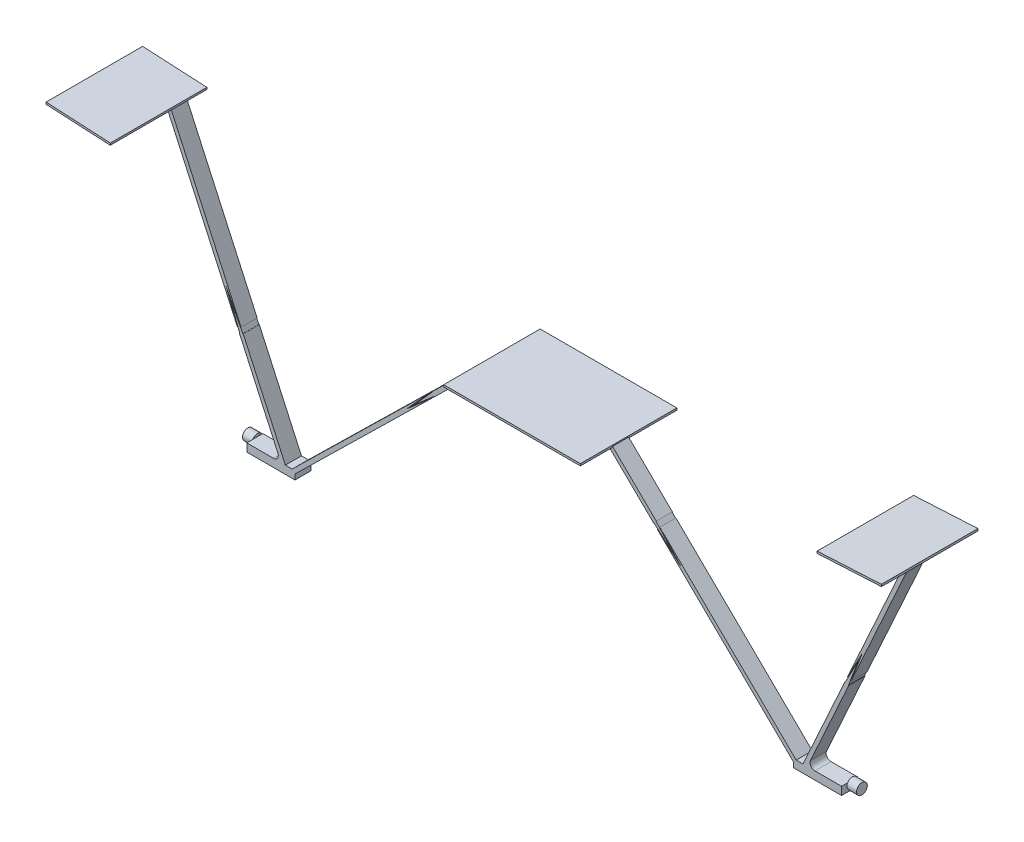
SolidWorks part; units mm, degrees
note: The reader was unsure of these and kept them because the rebuilt part matched: shared geometry of "Sketch1<4>", "Sketch1<6>", "Sketch1<7>", "Sketch1<8>".
ref_plane "Front Plane" through (0, 0, 0) normal (0, 0, 1) x (1, 0, 0)
ref_plane "Top Plane" through (0, 0, 0) normal (0, 1, 0) x (1, 0, 0)
ref_plane "Right Plane" through (0, 0, 0) normal (1, 0, 0) x (0, 0, -1)
sketch "Sketch1" plane through (0, 0, 0) normal (0, 0, 1) x (1, 0, 0)
  line L0 (0, 28.575) -> (748.2731, 67.7903) construction
  line L1 (-50.8, 28.575) -> (50.8, 28.575) construction
  line L2 (-50.8, 28.575) -> (-50.8, -28.575) construction
  line L3 (-50.8, -28.575) -> (50.8, -28.575) construction
  line L4 (50.8, 28.575) -> (50.8, -28.575) construction
  line L5 (-50.8, 28.575) -> (50.8, -28.575) construction
  line L6 (-50.8, -28.575) -> (50.8, 28.575) construction
  line L7 (0, 0) -> (0, -177.8) construction
  line L8 (0, -177.8) -> (203.2, -177.8) construction
  line L9 (0, 28.575) -> (304.3823, 44.527) construction
  line L10 (50.8, -28.575) -> (203.2, -177.8) construction
  line L11 (304.3823, 44.527) -> (203.2, -177.8) construction
  line L12 (0, -28.575) -> (50.8, -28.575)
  line L16 (0, -28.575) -> (0, -30.1625)
  line L18 (279.0171, 43.1977) -> (329.7475, 45.8563)
  line L19 (279.0171, 43.1977) -> (329.7475, 45.8563)
  line L20 (279.0171, 43.1977) -> (279.1002, 41.6123)
  line L21 (329.7475, 45.8563) -> (329.8306, 44.271)
  line L22 (279.1002, 41.6123) -> (329.8306, 44.271)
  line L23 (196.7149, -177.8) -> (234.8149, -177.8)
  line L24 (196.7149, -177.8) -> (196.7149, -171.45)
  line L25 (234.8149, -177.8) -> (234.8149, -171.45)
  line L26 (196.7149, -171.45) -> (234.8149, -171.45)
  line L27 (203.2, -177.8) -> (203.2, -146.05) construction
  line L28 (53.975, -29.4621) -> (198.984, -171.45)
  line L29 (50.1522, -30.1625) -> (196.7149, -173.6718)
  line L30 (207.8341, -171.45) -> (305.4279, 42.9921)
  line L31 (301.8543, 42.8048) -> (204.3457, -171.45)
  line L32 (0, -30.1625) -> (53.975, -30.1625)
  line L33 (53.975, -30.1625) -> (53.975, -28.575)
  line L34 (53.975, -28.575) -> (50.8, -28.575)
  point P0 (0, 0)
  point P14 (54.7565, -30.1625)
  point P16 (0, 0)
  point P19 (304.3823, 44.527)
  point P36 (0, 0)
  dimension "D1" = 101.6
  dimension "D2" = 57.15
  dimension "D3" = 749.3
  dimension "D4" = 3
  dimension "D5" = 177.8
  dimension "D6" = 203.2
  dimension "D7" = 304.8
  dimension "D8" = 3.175
  dimension "D9" = 1.5875
  dimension "D10" = 50.8
  dimension "D11" = 1.5875
  dimension "D12" = 6.35
  dimension "D13" = 31.75
  dimension "D14" = 38.1
  dimension "D15" = 1.5875
  dimension "D16" = 1.5875
  dimension "D17" = 1.5875
  dimension "D18" = 1.5875
extrude "Boss-Extrude1" add sketch "Sketch1" along normal mid plane 76.2 contours L12 L34 L33 L32 L16
extrude "Boss-Extrude2" add sketch "Sketch1<4>" along normal blind 76.2 separate body contours L20 L22 L21 L18
sketch "Sketch1<4>" plane through (0, 0, 0) normal (0, 0, 1) x (1, 0, 0) same geometry as "Sketch1"
extrude "Boss-Extrude8" add sketch "Sketch1<6>" along normal blind 12.7 separate body contours L26 L24 L23 L25
sketch "Sketch1<6>" plane through (0, 0, 0) normal (0, 0, 1) x (1, 0, 0) same geometry as "Sketch1"
extrude "Boss-Extrude9" add sketch "Sketch1<7>" along normal blind 12.7
sketch "Sketch1<7>" plane through (0, 0, 0) normal (0, 0, 1) x (1, 0, 0) same geometry as "Sketch1"
extrude "Boss-Extrude10" add sketch "Sketch1<8>" along normal blind 12.7 contours L22 L31 L26 L30
sketch "Sketch1<8>" plane through (0, 0, 0) normal (0, 0, 1) x (1, 0, 0) same geometry as "Sketch1"
sketch "Sketch2" plane through (234.8149, 0, 0) normal (1, 0, 0) x (0, 0, -1)
  line L0 (0, -177.8) -> (0, -171.45) construction
  line L1 (-12.7, -177.8) -> (0, -177.8) construction
  circle A0 centre (-4.2625, -173.5375) radius 4.2625
  dimension "D1" = 8.525
extrude "Boss-Extrude11" add sketch "Sketch2" along normal blind 7.62
sketch "printBeds" plane through (0, 0, 0) normal (0, 0, 1) x (1, 0, 0)
  line L0 (125.7236, -68.1503) -> (0, 57.5733) construction
  line L1 (125.7236, -68.1503) -> (0, -193.8739) construction
  line L2 (0, 57.5733) -> (-125.7236, -68.1503) construction
  line L3 (0, -193.8739) -> (-125.7236, -68.1503) construction
  line L4 (291.5515, 61.4763) -> (213.4818, -98.2672) construction
  line L5 (291.5515, 61.4763) -> (451.2949, -16.5934) construction
  line L6 (213.4818, -98.2672) -> (373.2252, -176.3369) construction
  line L7 (451.2949, -16.5934) -> (373.2252, -176.3369) construction
  line L8 (258.004, -217.3263) -> (253.5037, -39.5833) construction
  line L9 (258.004, -217.3263) -> (80.261, -221.8266) construction
  line L10 (253.5037, -39.5833) -> (75.7607, -44.0836) construction
  line L11 (80.261, -221.8266) -> (75.7607, -44.0836) construction
  dimension "D1" = 177.8
  dimension "D2" = 177.8
  dimension "D3" = 177.8
  dimension "D4" = 177.8
  dimension "D5" = 177.8
  dimension "D6" = 177.8
fillet "Fillet1" radius 3.81 4 edges at (207.8341, -171.45, 6.35) (305.4279, 42.9921, 6.35) (301.8543, 42.8048, 6.35) (50.1522, -30.1625, 6.35)
sketch "Sketch3" plane through (0, 0, 38.1) normal (0, 0, 1) x (1, 0, 0)
  line L0 (86.2682, -65.5261) -> (88.4895, -63.2575) construction
  line L7 (51.2631, -31.2502) -> (196.7149, -173.6718) construction
  line L14 (53.975, -29.4621) -> (198.984, -171.45) construction
  line L15 (86.2682, -65.5261) -> (105.5274, -82.1623) construction
  line L16 (105.5274, -82.1623) -> (88.4895, -63.2575) construction
  line L17 (105.5274, -82.1623) -> (87.3788, -64.3918) construction
  line L32 (86.1048, -65.7153) -> (108.391, -84.9662)
  line L33 (108.391, -84.9662) -> (88.6752, -63.0901)
  line L52 (86.4316, -65.3369) -> (102.6638, -79.3583)
  line L53 (102.6638, -79.3583) -> (88.3038, -63.4249)
  line L54 (86.1048, -65.7153) -> (86.4316, -65.3369)
  line L55 (88.6752, -63.0901) -> (88.3038, -63.4249)
  line L56 (237.6392, -98.2945) -> (240.529, -99.6097) construction
  line L57 (299.2551, 37.0934) -> (204.3457, -171.45) construction
  line L58 (210.2863, -166.0618) -> (304.4697, 40.8866) construction
  line L59 (237.6392, -98.2945) -> (249.6055, -75.8336) construction
  line L60 (249.6055, -75.8336) -> (240.529, -99.6097) construction
  line L61 (249.6055, -75.8336) -> (239.0841, -98.9521) construction
  line L62 (237.8599, -98.412) -> (247.9453, -79.4814)
  line L63 (247.9453, -79.4814) -> (240.2955, -99.5205)
  line L64 (237.4186, -98.1769) -> (251.2656, -72.1858)
  line L65 (251.2656, -72.1858) -> (240.7626, -99.6988)
  line L66 (240.2955, -99.5205) -> (240.7626, -99.6988)
  line L67 (237.4186, -98.1769) -> (237.8599, -98.412)
  dimension "D1" = 1.5875
  dimension "D2" = 0.25
  dimension "D3" = 0.25
  dimension "D4" = 25.4
  dimension "D5" = 1.5875
  dimension "D6" = 25.4
  dimension "D7" = 0.25
  dimension "D8" = 0.25
extrude "Cut-Extrude1" cut sketch "Sketch3" against normal through all
mirror "Mirror1" about plane through (0, 0, 0) normal (1, 0, 0) of bodies 127 122
mirror "Mirror2" about plane through (0, 0, 0) normal (1, 0, 0) of bodies 128 129 121 120
